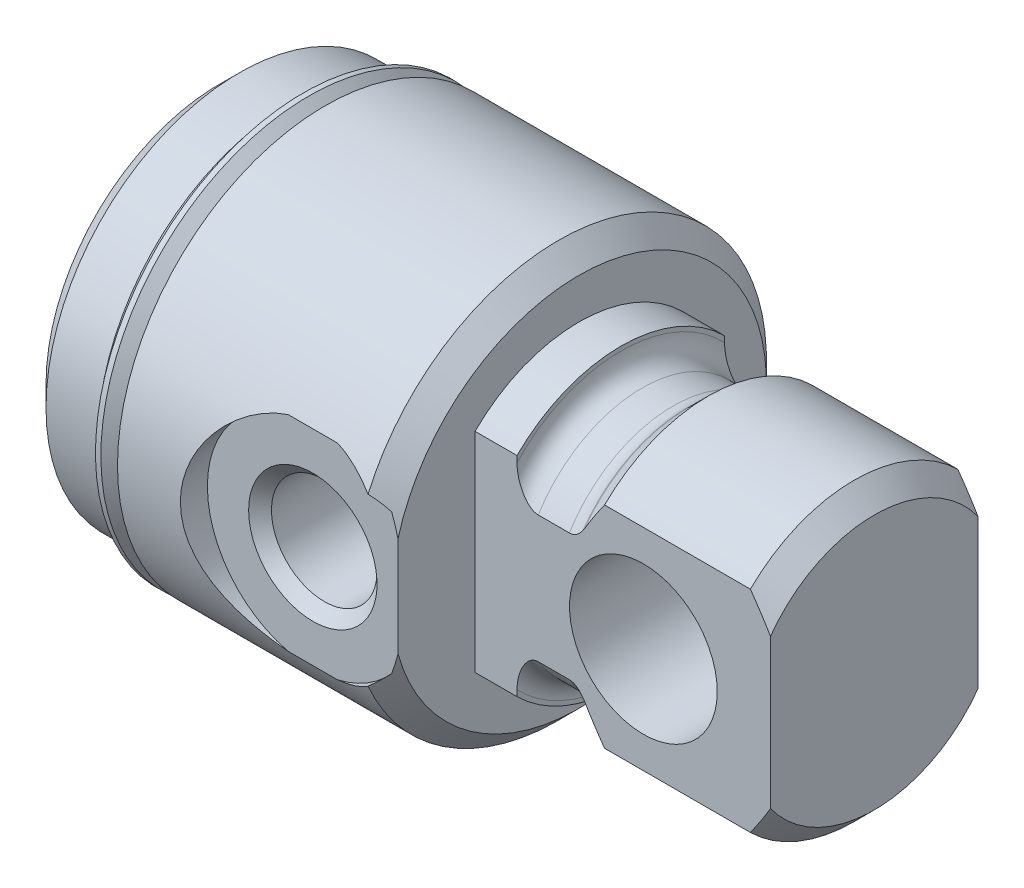
SolidWorks part; units mm, degrees
material "Cast Alloy Steel"
ref_plane "Front Plane" through (0, 0, 0) normal (0, 0, 1) x (1, 0, 0)
ref_plane "Top Plane" through (0, 0, 0) normal (0, 1, 0) x (1, 0, 0)
ref_plane "Right Plane" through (0, 0, 0) normal (1, 0, 0) x (0, 0, -1)
ref_plane "Plane1" through (24.6126, 0, 0) normal (1, 0, 0) x (0, 0, -1)
sketch "Sketch1" plane through (0, 0, 0) normal (0, 0, 1) x (1, 0, 0)
  line L0 (0, 0) -> (0, 6.5088)
  line L1 (0, 6.5088) -> (0.762, 7.2707)
  line L2 (0.762, 7.2707) -> (2.7178, 7.2707)
  line L3 (2.7178, 7.2707) -> (3.3528, 6.6357)
  line L4 (3.3528, 6.6357) -> (3.9878, 6.6357)
  line L5 (3.9878, 6.6357) -> (3.9878, 7.8105)
  line L6 (3.9878, 7.8105) -> (12.7508, 7.8105)
  line L7 (12.7508, 7.8105) -> (13.5128, 7.0485)
  line L8 (13.5128, 7.0485) -> (13.5128, 0)
  line L9 (13.5128, 0) -> (0, 0)
  line L10 (13.5128, 0) -> (0, 0) construction
revolve "Revolve1" add sketch "Sketch1" angle 360 about L10 reverse direction yes
sketch "Sketch2" plane through (0, 0, 0) normal (0, 0, 1) x (1, 0, 0)
  line L0 (13.5128, 0) -> (13.5128, 5.5309)
  line L1 (13.5128, 5.5309) -> (15.0876, 5.5309)
  line L2 (15.0876, 5.5309) -> (15.0876, 5.3721)
  line L3 (15.8877, 4.572) -> (17.0561, 4.572)
  line L4 (17.559, 4.7498) -> (17.6219, 4.8006)
  line L5 (17.6219, 4.8006) -> (18.3775, 5.5563)
  line L6 (18.3775, 5.5563) -> (23.857, 5.5563)
  line L7 (23.857, 5.5563) -> (24.6126, 4.8006)
  line L8 (24.6126, 4.8006) -> (24.6126, 0)
  line L9 (24.6126, 0) -> (13.5128, 0)
  line L10 (24.6126, 0) -> (13.5128, 0) construction
  arc A0 (15.0876, 5.3721) -> (15.8877, 4.572) centre (15.8877, 5.3721) ccw
  arc A1 (17.0561, 4.572) -> (17.559, 4.7498) centre (17.0561, 5.3721) ccw
revolve "Revolve2" add sketch "Sketch2" angle 360 about L10 reverse direction yes
cosmetic thread "Cosmetic Thread1" parameters "D1"=6.9907, "D2"=9.6012
sketch "Sketch3" plane through (24.6126, 0, 0) normal (1, 0, 0) x (0, 0, -1)
  line L0 (-15.621, -31.242) -> (15.621, -31.242)
  line L1 (15.621, -31.242) -> (15.621, 31.242)
  line L2 (15.621, 31.242) -> (-15.621, 31.242)
  line L3 (-15.621, 31.242) -> (-15.621, -31.242)
  line L4 (-3.8989, -15.621) -> (3.8989, -15.621)
  line L5 (3.8989, -15.621) -> (3.8989, 15.621)
  line L6 (3.8989, 15.621) -> (-3.8989, 15.621)
  line L7 (-3.8989, 15.621) -> (-3.8989, -15.621)
extrude "Cut-Extrude1" cut sketch "Sketch3" against normal blind 11.0998
ref_plane "Plane2" through (13.5128, 0, 0) normal (1, 0, 0) x (0, 0, -1)
hole_wizard "Hole1" positions "Sketch5" profile "Sketch4" legacy
sketch "Sketch5" plane through (0, 0, 0) normal (-1, 0, 0) x (0, 0, 1)
  point P0 (0, 0)
sketch "Sketch4" plane through (0, 0, 0) normal (0, 1, 0) x (0, 0, 1)
  line L0 (0, 0) -> (0, 13.4228)
  line L1 (0, 13.4228) -> (1.9558, 12.2936)
  line L2 (1.9558, 12.2936) -> (1.9558, 0)
  line L4 (1.9558, 0) -> (0, 0)
  line L6 (0, 13.4228) -> (-1.9558, 12.2936) construction
  line L7 (0, -4.2442) -> (0, 117.3081) construction
  dimension "Diameter" = 3.9116
  dimension "Depth" = 12.2936
  dimension "Drill Angle" = 120
ref_plane "Plane3" through (0, 0, 0) normal (0, 0.9998, 0.0175) x (1, 0, 0)
sketch "Sketch6" plane through (0, 0, 0) normal (0, 1, 0) x (1, 0, 0)
  line L0 (10.3124, 0) -> (12.2961, 0)
  line L1 (12.2961, 0) -> (12.2961, -6.3652)
  line L2 (12.2961, -6.3652) -> (12.7254, -6.7945)
  line L3 (12.7254, -6.7945) -> (14.2748, -6.7945)
  line L4 (14.2748, -6.7945) -> (14.2748, -7.8105)
  line L5 (14.2748, -7.8105) -> (10.3124, -7.8105)
  line L6 (10.3124, -7.8105) -> (10.3124, 0)
  line L7 (10.3124, -7.8105) -> (10.3124, 0) construction
revolve "Cut-Revolve1" cut sketch "Sketch6" angle 360 about L7 reverse direction yes
cosmetic thread "Cosmetic Thread2" parameters "D1"=4.8387, "D2"=4.826
ref_plane "Plane4" through (10.3124, 0, 0) normal (1, 0, 0) x (0, 0, -1)
ref_plane "Plane5" through (3.3528, 0, 0) normal (1, 0, 0) x (0, 0, -1)
sketch "Sketch7" plane through (0, 0, 0) normal (0, 0, 1) x (1, 0, 0)
  line L0 (3.1602, 7.7263) -> (3.8708, 7.0158)
  line L1 (3.8708, 6.8362) -> (3.6703, 6.6357)
  line L2 (3.6703, 6.6357) -> (3.3528, 6.6357)
  line L3 (3.3528, 6.6357) -> (3.3528, 6.3818)
  line L4 (3.3528, 6.3818) -> (3.9878, 6.3818)
  line L5 (3.9878, 6.3818) -> (3.9878, 7.1861)
  line L6 (3.9878, 7.1861) -> (3.3634, 7.8105)
  line L7 (3.3634, 7.8105) -> (3.1602, 7.8105)
  line L8 (3.1602, 7.8105) -> (3.1602, 7.7263)
  line L9 (3.9878, 0) -> (3.3528, 0) construction
  arc A0 (3.8708, 7.0158) -> (3.8708, 6.8362) centre (3.781, 6.926) cw
revolve "Revolve3" add sketch "Sketch7" angle 360 about L9 reverse direction yes
ref_plane "Plane6" through (24.7396, 0, 0) normal (1, 0, 0) x (0, 0, -1)
sketch "Sketch8" plane through (0, 0, 0) normal (0, 0, 1) x (1, 0, 0)
  circle A0 centre (19.8374, 0) radius 2.7749
extrude "Cut-Extrude2" cut sketch "Sketch8" along normal blind 5.8484 and the other way blind 5.8484
ref_plane "Plane7" through (15.0876, 0, 0) normal (1, 0, 0) x (0, 0, -1)
ref_plane "Plane8" through (19.9644, 0, 0) normal (1, 0, 0) x (0, 0, -1)
ref_plane "Plane9" through (19.8374, 0, 0) normal (1, 0, 0) x (0, 0, -1)
ref_plane "Plane10" through (24.6126, 0, 0) normal (1, 0, 0) x (0, 0, -1)
ref_plane "Plane11" through (0, 0, 0) normal (0, 0, 1) x (1, 0, 0)
ref_plane "Plane12" through (15.0876, 0, 0) normal (1, 0, 0) x (0, 0, -1)
ref_plane "Plane13" through (0, 0, 0) normal (0, 1, 0) x (1, 0, 0)
ref_plane "Plane14" through (0, 0, 0) normal (0, 1, 0) x (1, 0, 0)
ref_plane "Plane15" through (13.5128, 0, 0) normal (1, 0, 0) x (0, 0, -1)
ref_plane "1 XY" through (15.0876, 0, 0) normal (1, 0, 0) x (0, 0, -1)
ref_plane "1 XZ" through (0, 0, 0) normal (0, -1, 0) x (-1, 0, 0)
ref_plane "1 YZ" through (0, 0, 0) normal (0, 0, -1) x (-1, 0, 0)
ref_axis "1 X" through (15.0876, 0, 80.9) along (0, 0, -1)
ref_axis "1 Y" through (15.0876, -50, 0) along (0, 1, 0)
ref_axis "1 Z" through (80.9, 0, 0) along (-1, 0, 0)
sketch3d "1"
  point P0 (15.0876, 0, 0)
ref_plane "c1 XY" through (0, 0, 0) normal (0, 0, 1) x (1, 0, 0)
ref_plane "c1 XZ" through (0, 5.5309, 0) normal (0, -1, 0) x (-1, 0, 0)
ref_plane "c1 YZ" through (13.5128, 0, 0) normal (1, 0, 0) x (0, 0, -1)
ref_axis "c1 X" through (-80.9, 5.5309, 0) along (1, 0, 0)
ref_axis "c1 Y" through (13.5128, -50, 0) along (0, 1, 0)
ref_axis "c1 Z" through (13.5128, 5.5309, 80.9) along (0, 0, -1)
sketch3d "c1"
  point P0 (13.5128, 5.5309, 0)
ref_plane "c2 XY" through (0, 0, 0) normal (0, 0, 1) x (1, 0, 0)
ref_plane "c2 XZ" through (0, -5.5309, 0) normal (0, -1, 0) x (-1, 0, 0)
ref_plane "c2 YZ" through (13.5128, 0, 0) normal (1, 0, 0) x (0, 0, -1)
ref_axis "c2 X" through (-80.9, -5.5309, 0) along (1, 0, 0)
ref_axis "c2 Y" through (13.5128, -50, 0) along (0, 1, 0)
ref_axis "c2 Z" through (13.5128, -5.5309, 80.9) along (0, 0, -1)
sketch3d "c2"
  point P0 (13.5128, -5.5309, 0)
ref_plane "cc1 XY" through (0, 0, 0) normal (0, 0, 1) x (1, 0, 0)
ref_plane "cc1 XZ" through (0, 0, 0) normal (0, -1, 0) x (-1, 0, 0)
ref_plane "cc1 YZ" through (13.5128, 0, 0) normal (1, 0, 0) x (0, 0, -1)
ref_axis "cc1 X" through (-80.9, 0, 0) along (1, 0, 0)
ref_axis "cc1 Y" through (13.5128, -50, 0) along (0, 1, 0)
ref_axis "cc1 Z" through (13.5128, 0, 80.9) along (0, 0, -1)
sketch3d "cc1"
  point P0 (13.5128, 0, 0)
ref_plane "cc2 XY" through (0, 0, 0) normal (0, 0, 1) x (1, 0, 0)
ref_plane "cc2 XZ" through (0, 0, 0) normal (0, -1, 0) x (-1, 0, 0)
ref_plane "cc2 YZ" through (15.0876, 0, 0) normal (1, 0, 0) x (0, 0, -1)
ref_axis "cc2 X" through (-80.9, 0, 0) along (1, 0, 0)
ref_axis "cc2 Y" through (15.0876, -50, 0) along (0, 1, 0)
ref_axis "cc2 Z" through (15.0876, 0, 80.9) along (0, 0, -1)
sketch3d "cc2"
  point P0 (15.0876, 0, 0)
ref_plane "lovra1 XY" through (19.9644, 0, 0) normal (1, 0, 0) x (0, 0, -1)
ref_plane "lovra1 XZ" through (0, 0, 0) normal (0, -1, 0) x (-1, 0, 0)
ref_plane "lovra1 YZ" through (0, 0, 0) normal (0, 0, -1) x (-1, 0, 0)
ref_axis "lovra1 X" through (19.9644, 0, 80.9) along (0, 0, -1)
ref_axis "lovra1 Y" through (19.9644, -50, 0) along (0, 1, 0)
ref_axis "lovra1 Z" through (80.9, 0, 0) along (-1, 0, 0)
sketch3d "lovra1"
  point P0 (19.9644, 0, 0)
ref_plane "lovra2 XY" through (19.9644, 0, 0) normal (1, 0, 0) x (0, 0, -1)
ref_plane "lovra2 XZ" through (0, 6.2865, 0) normal (0, -1, 0) x (-1, 0, 0)
ref_plane "lovra2 YZ" through (0, 0, 0) normal (0, 0, -1) x (-1, 0, 0)
ref_axis "lovra2 X" through (19.9644, 6.2865, 80.9) along (0, 0, -1)
ref_axis "lovra2 Y" through (19.9644, -50, 0) along (0, 1, 0)
ref_axis "lovra2 Z" through (80.9, 6.2865, 0) along (-1, 0, 0)
sketch3d "lovra2"
  point P0 (19.9644, 6.2865, 0)
ref_plane "lovra21 XY" through (0, 0, 0) normal (1, 0, 0) x (0, 0, -1)
ref_plane "lovra21 XZ" through (0, 0, 0) normal (0, -1, 0) x (-1, 0, 0)
ref_plane "lovra21 YZ" through (0, 0, 5.2705) normal (0, 0, -1) x (-1, 0, 0)
ref_axis "lovra21 X" through (0, 0, 80.9) along (0, 0, -1)
ref_axis "lovra21 Y" through (0, -50, 5.2705) along (0, 1, 0)
ref_axis "lovra21 Z" through (80.9, 0, 5.2705) along (-1, 0, 0)
sketch3d "lovra21"
  point P0 (0, 0, 5.2705)
ref_plane "lovra22 XY" through (0, 0, 0) normal (1, 0, 0) x (0, 0, -1)
ref_plane "lovra22 XZ" through (0, 0, 0) normal (0, -1, 0) x (-1, 0, 0)
ref_plane "lovra22 YZ" through (0, 0, -5.2705) normal (0, 0, -1) x (-1, 0, 0)
ref_axis "lovra22 X" through (0, 0, 80.9) along (0, 0, -1)
ref_axis "lovra22 Y" through (0, -50, -5.2705) along (0, 1, 0)
ref_axis "lovra22 Z" through (80.9, 0, -5.2705) along (-1, 0, 0)
sketch3d "lovra22"
  point P0 (0, 0, -5.2705)
ref_plane "lovra3 XY" through (19.9644, 0, 0) normal (1, 0, 0) x (0, 0, -1)
ref_plane "lovra3 XZ" through (0, -6.2865, 0) normal (0, -1, 0) x (-1, 0, 0)
ref_plane "lovra3 YZ" through (0, 0, 0) normal (0, 0, -1) x (-1, 0, 0)
ref_axis "lovra3 X" through (19.9644, -6.2865, 80.9) along (0, 0, -1)
ref_axis "lovra3 Y" through (19.9644, -50, 0) along (0, 1, 0)
ref_axis "lovra3 Z" through (80.9, -6.2865, 0) along (-1, 0, 0)
sketch3d "lovra3"
  point P0 (19.9644, -6.2865, 0)
ref_plane "olen XY" through (19.8374, 0, 0) normal (1, 0, 0) x (0, 0, -1)
ref_plane "olen XZ" through (0, 0, 0) normal (0, -1, 0) x (-1, 0, 0)
ref_plane "olen YZ" through (0, 0, 0) normal (0, 0, -1) x (-1, 0, 0)
ref_axis "olen X" through (19.8374, 0, 80.9) along (0, 0, -1)
ref_axis "olen Y" through (19.8374, -50, 0) along (0, 1, 0)
ref_axis "olen Z" through (80.9, 0, 0) along (-1, 0, 0)
sketch3d "olen"
  point P0 (19.8374, 0, 0)
ref_plane "p1 XY" through (24.6126, 0, 0) normal (1, 0, 0) x (0, 0, -1)
ref_plane "p1 XZ" through (0, 0, 0) normal (0, -1, 0) x (-1, 0, 0)
ref_plane "p1 YZ" through (0, 0, 3.9624) normal (0, 0, -1) x (-1, 0, 0)
ref_axis "p1 X" through (24.6126, 0, 80.9) along (0, 0, -1)
ref_axis "p1 Y" through (24.6126, -50, 3.9624) along (0, 1, 0)
ref_axis "p1 Z" through (80.9, 0, 3.9624) along (-1, 0, 0)
sketch3d "p1"
  point P0 (24.6126, 0, 3.9624)
ref_plane "p2 XY" through (24.6126, 0, 0) normal (1, 0, 0) x (0, 0, -1)
ref_plane "p2 XZ" through (0, 0, 0) normal (0, -1, 0) x (-1, 0, 0)
ref_plane "p2 YZ" through (0, 0, -3.9624) normal (0, 0, -1) x (-1, 0, 0)
ref_axis "p2 X" through (24.6126, 0, 80.9) along (0, 0, -1)
ref_axis "p2 Y" through (24.6126, -50, -3.9624) along (0, 1, 0)
ref_axis "p2 Z" through (80.9, 0, -3.9624) along (-1, 0, 0)
sketch3d "p2"
  point P0 (24.6126, 0, -3.9624)
ref_plane "port XY" through (0, 0, 0) normal (0, 0, 1) x (1, 0, 0)
ref_plane "port XZ" through (0, 0, 0) normal (0, -1, 0) x (-1, 0, 0)
ref_plane "port YZ" through (10.3124, 0, 0) normal (1, 0, 0) x (0, 0, -1)
ref_axis "port X" through (-80.9, 0, 0) along (1, 0, 0)
ref_axis "port Y" through (10.3124, -50, 0) along (0, 1, 0)
ref_axis "port Z" through (10.3124, 0, 80.9) along (0, 0, -1)
sketch3d "port"
  point P0 (10.3124, 0, 0)
ref_plane "port2 XY" through (24.6126, 0, 0) normal (1, 0, 0) x (0, 0, -1)
ref_plane "port2 XZ" through (0, 0, 0) normal (0, -1, 0) x (-1, 0, 0)
ref_plane "port2 YZ" through (0, 0, 0) normal (0, 0, -1) x (-1, 0, 0)
ref_axis "port2 X" through (24.6126, 0, 80.9) along (0, 0, -1)
ref_axis "port2 Y" through (24.6126, -50, 0) along (0, 1, 0)
ref_axis "port2 Z" through (80.9, 0, 0) along (-1, 0, 0)
sketch3d "port2"
  point P0 (24.6126, 0, 0)
ref_plane "thd1 XY" through (24.6126, 0, 0) normal (1, 0, 0) x (0, 0, -1)
ref_plane "thd1 XZ" through (0, 0, 0) normal (0, -1, 0) x (-1, 0, 0)
ref_plane "thd1 YZ" through (0, 0, 5.5563) normal (0, 0, -1) x (-1, 0, 0)
ref_axis "thd1 X" through (24.6126, 0, 80.9) along (0, 0, -1)
ref_axis "thd1 Y" through (24.6126, -50, 5.5563) along (0, 1, 0)
ref_axis "thd1 Z" through (80.9, 0, 5.5563) along (-1, 0, 0)
sketch3d "thd1"
  point P0 (24.6126, 0, 5.5563)
ref_plane "thd2 XY" through (24.6126, 0, 0) normal (1, 0, 0) x (0, 0, -1)
ref_plane "thd2 XZ" through (0, 0, 0) normal (0, -1, 0) x (-1, 0, 0)
ref_plane "thd2 YZ" through (0, 0, -5.5563) normal (0, 0, -1) x (-1, 0, 0)
ref_axis "thd2 X" through (24.6126, 0, 80.9) along (0, 0, -1)
ref_axis "thd2 Y" through (24.6126, -50, -5.5563) along (0, 1, 0)
ref_axis "thd2 Z" through (80.9, 0, -5.5563) along (-1, 0, 0)
sketch3d "thd2"
  point P0 (24.6126, 0, -5.5563)
ref_plane "to_mounting_bracket XY" through (13.5128, 0, 0) normal (1, 0, 0) x (0, 0, -1)
ref_plane "to_mounting_bracket XZ" through (0, 0, 0) normal (0, -1, 0) x (-1, 0, 0)
ref_plane "to_mounting_bracket YZ" through (0, 0, 0) normal (0, 0, -1) x (-1, 0, 0)
ref_axis "to_mounting_bracket X" through (13.5128, 0, 80.9) along (0, 0, -1)
ref_axis "to_mounting_bracket Y" through (13.5128, -50, 0) along (0, 1, 0)
ref_axis "to_mounting_bracket Z" through (80.9, 0, 0) along (-1, 0, 0)
sketch3d "to_mounting_bracket"
  point P0 (13.5128, 0, 0)
ref_plane "to_nut XY" through (15.0876, 0, 0) normal (1, 0, 0) x (0, 0, -1)
ref_plane "to_nut XZ" through (0, 0, 0) normal (0, -1, 0) x (-1, 0, 0)
ref_plane "to_nut YZ" through (0, 0, 0) normal (0, 0, -1) x (-1, 0, 0)
ref_axis "to_nut X" through (15.0876, 0, 80.9) along (0, 0, -1)
ref_axis "to_nut Y" through (15.0876, -50, 0) along (0, 1, 0)
ref_axis "to_nut Z" through (80.9, 0, 0) along (-1, 0, 0)
sketch3d "to_nut"
  point P0 (15.0876, 0, 0)
ref_plane "to_pin XY" through (0, 0, 0) normal (0, 0, 1) x (1, 0, 0)
ref_plane "to_pin XZ" through (0, 0, 0) normal (0, -1, 0) x (-1, 0, 0)
ref_plane "to_pin YZ" through (19.8374, 0, 0) normal (1, 0, 0) x (0, 0, -1)
ref_axis "to_pin X" through (-80.9, 0, 0) along (1, 0, 0)
ref_axis "to_pin Y" through (19.8374, -50, 0) along (0, 1, 0)
ref_axis "to_pin Z" through (19.8374, 0, 80.9) along (0, 0, -1)
sketch3d "to_pin"
  point P0 (19.8374, 0, 0)
ref_plane "to_screw XY" through (0, 0, 0) normal (0, 1, 0) x (1, 0, 0)
ref_plane "to_screw XZ" through (0, 0, 0) normal (0, 0, 1) x (1, 0, 0)
ref_plane "to_screw YZ" through (10.3124, 0, 0) normal (1, 0, 0) x (0, 0, -1)
ref_axis "to_screw X" through (-80.9, 0, 0) along (1, 0, 0)
ref_axis "to_screw Y" through (10.3124, 0, 50) along (0, 0, -1)
ref_axis "to_screw Z" through (10.3124, 50, 0) along (0, -1, 0)
sketch3d "to_screw"
  point P0 (10.3124, 0, 0)
ref_plane "to_tube XY" through (3.3528, 0, 0) normal (1, 0, 0) x (0, 0, -1)
ref_plane "to_tube XZ" through (0, 0, 0) normal (0, -1, 0) x (-1, 0, 0)
ref_plane "to_tube YZ" through (0, 0, 0) normal (0, 0, -1) x (-1, 0, 0)
ref_axis "to_tube X" through (3.3528, 0, 80.9) along (0, 0, -1)
ref_axis "to_tube Y" through (3.3528, -50, 0) along (0, 1, 0)
ref_axis "to_tube Z" through (80.9, 0, 0) along (-1, 0, 0)
sketch3d "to_tube"
  point P0 (3.3528, 0, 0)
